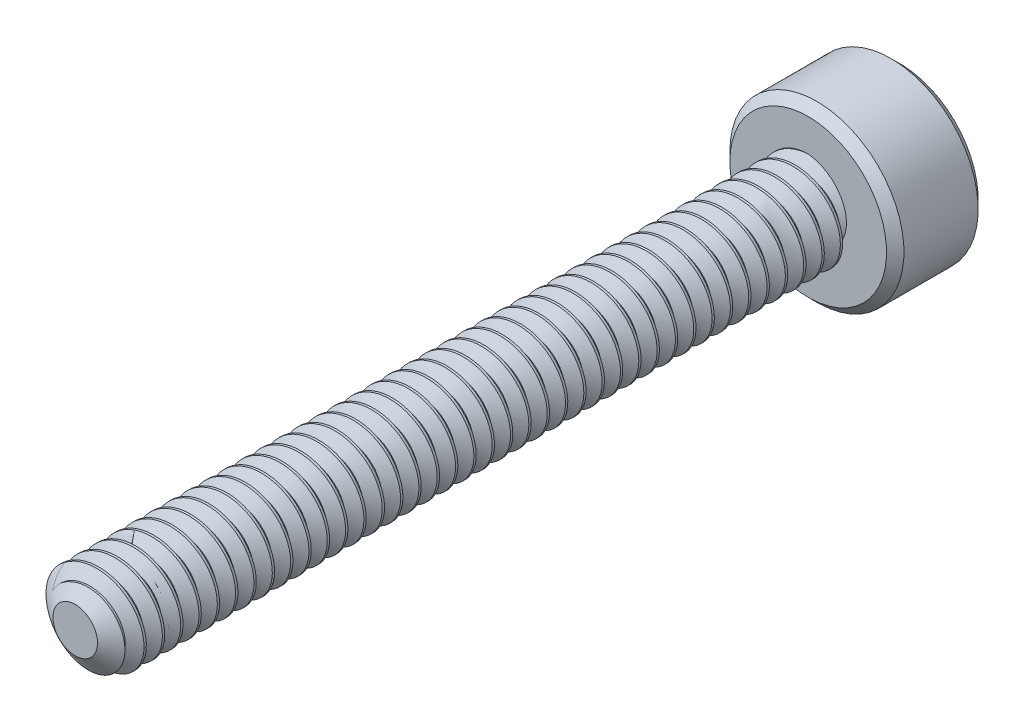
SolidWorks part; units mm, degrees
other "DetailItem1"
ref_plane "Front Plane" through (0, 0, 0) normal (0, 0, 1) x (1, 0, 0)
ref_plane "Top Plane" through (0, 0, 0) normal (0, 1, 0) x (1, 0, 0)
ref_plane "Right Plane" through (0, 0, 0) normal (1, 0, 0) x (0, 0, -1)
sketch "Sketch1" plane through (0, 0, 0) normal (0, 0, 1) x (1, 0, 0)
  circle A0 centre (0, 0) radius 1
  dimension "OD" = 2
extrude "Extrude1" add sketch "Sketch1" against normal blind 16
sketch "Sketch2" plane through (0, 0, 0) normal (0, 0, 1) x (1, 0, 0)
  circle A0 centre (0, 0) radius 1 construction
  circle A1 centre (0, 0) radius 1
curve "Helix/Spiral1" pitch 0.4 height 16.4 turns 41 parameters "pitch"=0.4
sketch "Sketch3" plane through (0, 0, 0) normal (1, 0, 0) x (0, 0, -1)
  line L0 (-0.35, 1) -> (-0.2, 0.7402)
  line L1 (-0.2, 0.7402) -> (-0.15, 0.7402)
  line L2 (-0.15, 0.7402) -> (0, 1)
  line L3 (-0.35, 1) -> (0, 1)
  line L4 (-0.175, 1) -> (-0.175, 0.7402) construction
  line L5 (-0.275, 0.8701) -> (-0.075, 0.8701) construction
  line L6 (0, 1) -> (0, -1) construction
  dimension "D1" = 0.05
  dimension "D2" = 0.2
  dimension "D3" = 60
sweep "Cut-Sweep1" cut profiles "Sketch3" path "Helix/Spiral1"
sketch "Sketch4" plane through (0, 0, 0) normal (1, 0, 0) x (0, 0, -1)
  line L0 (0.3598, 1) -> (0, 0.4862)
  line L1 (0, 0.4862) -> (0, 1)
  line L2 (0.3598, 1) -> (0, 1)
  line L3 (-0.35, 1) -> (0, 1) construction
  line L4 (0, 0) -> (7.0209, 0) construction
  dimension "D1" = 55
  dimension "D2" = 0.254
revolve "Cut-Revolve1" cut sketch "Sketch4" angle 360 about L4
sketch "Sketch6" plane through (0, 0, -16) normal (0, 0, -1) x (-1, 0, 0)
  circle A0 centre (0, 0) radius 1.9
  dimension "head dia" = 3.8
extrude "Extrude2" add sketch "Sketch6" along normal blind 2
sketch "Sketch7" plane through (0, 0, -18) normal (0, 0, -1) x (-1, 0, 0)
  line L1 (0, 0.866) -> (-0.75, 0.433)
  line L2 (-0.75, 0.433) -> (-0.75, -0.433)
  line L3 (-0.75, -0.433) -> (0, -0.866)
  line L4 (0, -0.866) -> (0.75, -0.433)
  line L5 (0.75, -0.433) -> (0.75, 0.433)
  line L6 (0.75, 0.433) -> (0, 0.866)
  circle A0 centre (0, 0) radius 0.75 construction
  dimension "hex dia" = 1.5
extrude "Cut-Extrude1" cut sketch "Sketch7" against normal blind 1.125
sketch "Sketch8" plane through (0, 0, -18) normal (0, 0, -1) x (-1, 0, 0)
  circle A0 centre (0, 0) radius 0.866
extrude "Cut-Extrude2" cut sketch "Sketch8" against normal through all draft 45
chamfer "Chamfer1" distance 0.19 angle 45 2 edges at (-1.9, 0, -18) (-1.9, 0, -16)
sketch "Sketch10" plane through (0, 0, -16) normal (0, 0, 1) x (1, 0, 0)
  circle A1 centre (0, 0) radius 1
  circle A2 centre (0, 0) radius 1
  dimension "D1" = 0
ref_plane "Plane1" through (0, 0, 0) normal (0, 0, 1) x (1, 0, 0)
extrude "partial thread" [suppressed] add sketch "Sketch10" along normal up to surface (36 mm away) separate body
chamfer "Chamfer2" [suppressed] distance 0.04 angle 45
combine bodies "Combine1" [suppressed] operation type add bodies to combine 107 108
sketch "Sketch9" plane through (0, 0, 0) normal (1, 0, 0) x (0, 0, -1)
  line L0 (0, 1) -> (0, -1) construction
  line L1 (1, 1) -> (1, -1) construction
  dimension "D1" = 1
equation "\"D3@Helix/Spiral1\" = \"screw length@Extrude1\"+\"pitch@Helix/Spiral1\""
equation "\"D1@Sketch3\" = \"pitch@Helix/Spiral1\"*.125"
equation "\"D2@Sketch3\" = \"pitch@Helix/Spiral1\"*.5"
equation "\"D1@Cut-Extrude1\" = \"hex dia@Sketch7\"*.75"
equation "\"D1@Chamfer1\" = \"head dia@Sketch6\"*.05"
equation "\"D1@Sketch9\" = \"pitch@Helix/Spiral1\"*2.5"
equation "\"D1@Chamfer2\"=\"OD@Sketch1\"*.02"
